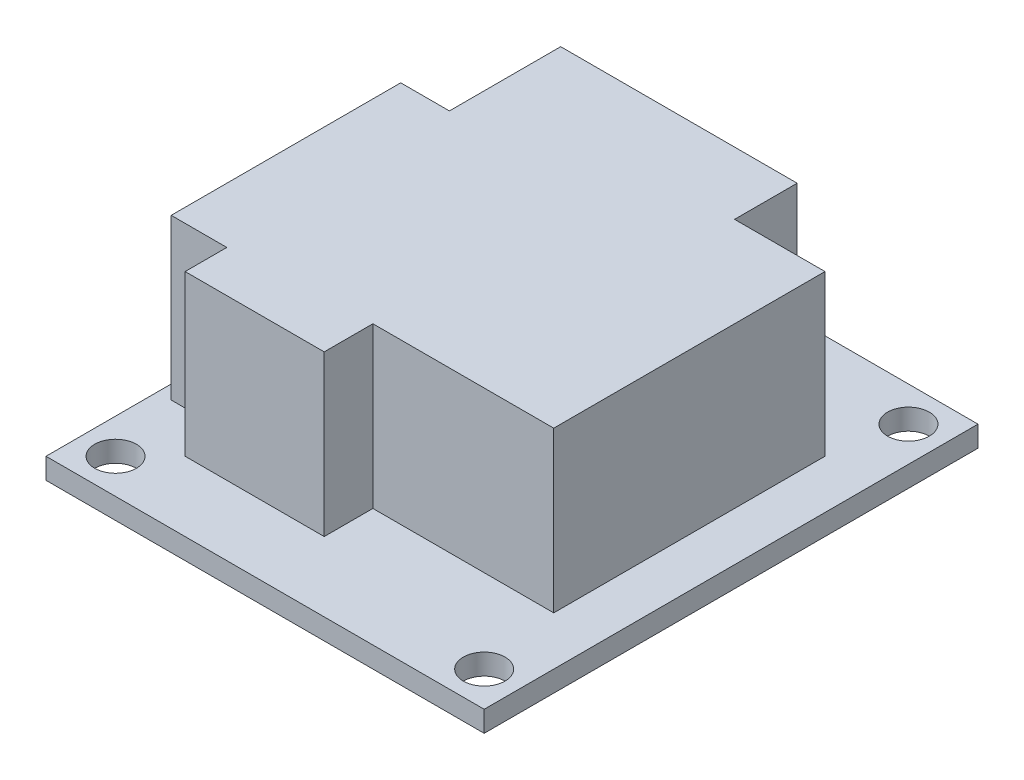
SolidWorks part; units mm, degrees
ref_plane "Front Plane" through (0, 0, 0) normal (0, 0, 1) x (1, 0, 0)
ref_plane "Top Plane" through (0, 0, 0) normal (0, 1, 0) x (1, 0, 0)
ref_plane "Right Plane" through (0, 0, 0) normal (1, 0, 0) x (0, 0, -1)
sketch "Sketch1" plane through (1.5043, 0, 3.0996) normal (0, 1, 0) x (1, 0, 0)
  line L0 (-11.25, -17.75) -> (-11.25, -9.75)
  line L1 (15.75, -42.25) -> (-15.75, -42.25)
  line L2 (15.75, -42.25) -> (15.75, -6.75)
  line L3 (15.75, -6.75) -> (-15.75, -6.75)
  line L4 (-15.75, -42.25) -> (-15.75, -6.75)
  line L5 (15.75, -42.25) -> (-15.75, -6.75) construction
  line L6 (15.75, -6.75) -> (-15.75, -42.25) construction
  line L7 (-13.25, -39.75) -> (13.25, -39.75) construction
  line L8 (-13.25, -39.75) -> (-13.25, -9.25) construction
  line L9 (-13.25, -9.25) -> (13.25, -9.25) construction
  line L10 (13.25, -39.75) -> (13.25, -9.25) construction
  line L11 (-13.25, -39.75) -> (13.25, -9.25) construction
  line L12 (-13.25, -9.25) -> (13.25, -39.75) construction
  line L13 (-11.25, -9.75) -> (5.75, -9.75)
  line L14 (5.75, -9.75) -> (5.75, -14.25)
  line L15 (5.75, -14.25) -> (12.25, -14.25)
  line L16 (12.25, -14.25) -> (12.25, -33.75)
  line L17 (12.25, -33.75) -> (-0.75, -33.75)
  line L18 (-0.75, -33.75) -> (-0.75, -37.25)
  line L19 (-0.75, -37.25) -> (-10.75, -37.25)
  line L20 (-10.75, -37.25) -> (-10.75, -34.25)
  line L21 (-10.75, -34.25) -> (-14.75, -34.25)
  line L22 (-14.75, -34.25) -> (-14.75, -17.75)
  line L23 (-14.75, -17.75) -> (-11.25, -17.75)
  line L24 (92.25, 3.25) -> (-17.75, 3.25) construction
  line L25 (-15.75, -64.75) -> (-15.75, 3.25) construction
  circle A0 centre (13.25, -9.25) radius 1.5
  circle A1 centre (-13.25, -9.25) radius 1.5
  circle A2 centre (-13.25, -39.75) radius 1.5
  circle A3 centre (13.25, -39.75) radius 1.5
  point P0 (0, -24.5)
  point P5 (0, -1.6566)
  point P6 (0, -24.5)
  point P27 (15.75, -24.5)
  point P30 (0, 0)
  point P31 (0, 0)
  dimension "D5" = 3
  dimension "D1" = 31.5
  dimension "D2" = 35.5
  dimension "D3" = 30.5
  dimension "D4" = 26.5
  dimension "D6" = 5
  dimension "D7" = 3.5
  dimension "D8" = 3
  dimension "D9" = 1
  dimension "D10" = 8
  dimension "D11" = 5
  dimension "D12" = 10
  dimension "D13" = 19.5
  dimension "D14" = 8.5
  dimension "D15" = 10
  dimension "D16" = 17
  dimension "D17" = 16.5
  dimension "D18" = 0
  dimension "D19" = 27.75
  dimension "D20" = 15.75
extrude "Boss-Extrude1" add sketch "Sketch1" along normal blind 1.5 contours L23 L22 L21 L20 L19 L18 L17 L16 L15 L14 L13 L0 | L4 L1 L2 L3 A3 A2 A1 A0 L22 L23 L0 L13 L14 L15 L16 L17 L18 L19 L20 L21 region at (0.0132, 0, 26.4664) region at (1.5043, 0, 44.875)
extrude "Boss-Extrude2" add sketch "Sketch1<3>" along normal blind 13 contours L23 L22 L21 L20 L19 L18 L17 L16 L15 L14 L13 L0 region at (0.0132, 0, 26.4664)
sketch "Sketch1<3>" plane through (1.5043, 0, 3.0996) normal (0, 1, 0) x (1, 0, 0) same geometry as "Sketch1"
extrude "Boss-Extrude3" add sketch "Sketch1<4>" against normal blind 1 contours L23 L22 L21 L20 L19 L18 L17 L16 L15 L14 L13 L0 region at (0.0132, 0, 26.4664)
sketch "Sketch1<4>" plane through (1.5043, 0, 3.0996) normal (0, 1, 0) x (1, 0, 0) same geometry as "Sketch1"
